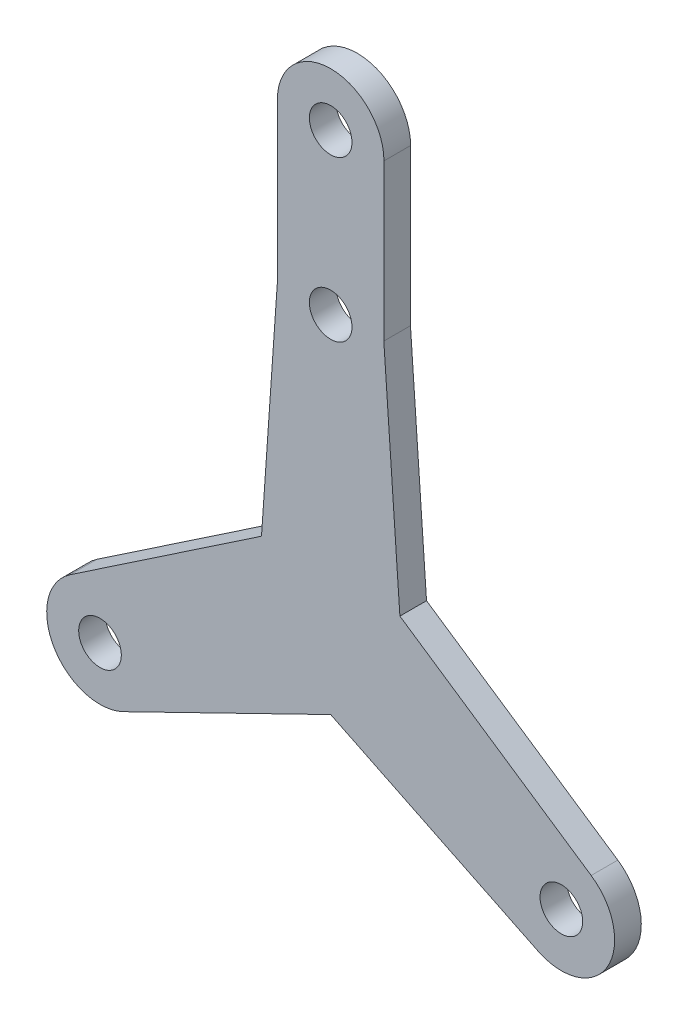
SolidWorks part; units mm, degrees
ref_plane "Front Plane" through (0, 0, 0) normal (0, 0, 1) x (1, 0, 0)
ref_plane "Top Plane" through (0, 0, 0) normal (0, 1, 0) x (1, 0, 0)
ref_plane "Right Plane" through (0, 0, 0) normal (1, 0, 0) x (0, 0, -1)
ref_axis "X" through (-88.99, 0, 0) along (1, 0, 0)
ref_axis "Y" through (0, 55, 0) along (0, -1, 0)
ref_axis "Z" through (0, 0, -88.99) along (0, 0, 1)
sketch "Sketch1" plane through (0, 0, 0) normal (0, 0, 1) x (1, 0, 0)
  line L0 (0, 0) -> (0, -50) construction
  line L1 (0, -50) -> (-43.3013, -75) construction
  line L2 (0, -50) -> (43.3013, -75) construction
  line L3 (0, -50) -> (-12.9904, -42.5) construction
  line L4 (-38.9163, -83.9873) -> (0, -65)
  line L5 (0, -65) -> (38.9163, -83.9873)
  line L6 (-12.9904, -42.5) -> (0, -50) construction
  line L7 (0, -50) -> (12.9904, -42.5) construction
  line L8 (-12.9904, -42.5) -> (-48.8921, -66.7089)
  line L9 (48.8921, -66.7089) -> (12.9904, -42.5)
  line L10 (-12.9904, -42.5) -> (-9.9757, 0.6962)
  line L11 (12.9904, -42.5) -> (9.9757, 0.6962)
  line L12 (0, 0) -> (0, 30) construction
  line L13 (-10, 30) -> (-9.9757, 0.6962)
  line L14 (10, 30) -> (9.9757, 0.6962)
  circle A0 centre (-43.3013, -75) radius 10 construction
  circle A1 centre (43.3013, -75) radius 10 construction
  circle A2 centre (0, -50) radius 15 construction
  circle A3 centre (0, 0) radius 10 construction
  arc A4 (-48.8921, -66.7089) -> (-38.9163, -83.9873) centre (-43.3013, -75) ccw
  arc A5 (48.8921, -66.7089) -> (38.9163, -83.9873) centre (43.3013, -75) cw
  circle A7 centre (0, 30) radius 10 construction
  arc A8 (-10, 30) -> (10, 30) centre (0, 30) cw
  dimension "D6" = 20
  dimension "D7" = 20
  dimension "D8" = 30
  dimension "D9" = 20
  dimension "D13" = 20
  dimension "D1" = 50
  dimension "D2" = 50
  dimension "D3" = 50
  dimension "D4" = 120
  dimension "D5" = 120
  dimension "D10" = 60
  dimension "D11" = 60
  dimension "D12" = 30
extrude "Boss-Extrude1" add sketch "Sketch1" along normal blind 5 contours L11 L14 A8 L13 L10 L8 A4 L4 L5 A5 L9
sketch "Sketch3" plane through (0, 0, 0) normal (0, 0, -1) x (-1, 0, 0)
  circle A0 centre (0, 30) radius 4
  circle A1 centre (0, 0) radius 4
  circle A2 centre (-43.3013, -75) radius 4
  circle A3 centre (43.3013, -75) radius 4
  dimension "D1" = 8
  dimension "D2" = 8
  dimension "D3" = 8
  dimension "D4" = 8
extrude "Cut-Extrude1" cut sketch "Sketch3" against normal blind 5
